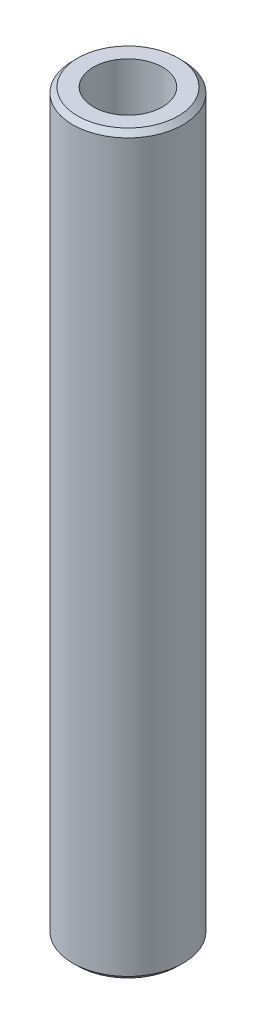
SolidWorks part; units mm, degrees
ref_plane "Front Plane" through (0, 0, 0) normal (0, 0, 1) x (1, 0, 0)
ref_plane "Top Plane" through (0, 0, 0) normal (0, 1, 0) x (1, 0, 0)
ref_plane "Right Plane" through (0, 0, 0) normal (1, 0, 0) x (0, 0, -1)
sketch "Sketch1" plane through (0, 0, 0) normal (0, 1, 0) x (1, 0, 0)
  circle A0 centre (0, 0) radius 45
  dimension "SHAFT_OD" = 90
extrude "Boss-Extrude1" add sketch "Sketch1" along normal blind 600
sketch "Sketch2" plane through (0, 0, 0) normal (0, 1, 0) x (1, 0, 0)
  circle A0 centre (0, 0) radius 28.1488
  dimension "BORE_D" = 56.2976
extrude "Cut-Extrude1" cut sketch "Sketch2" along normal through all
chamfer "Chamfer1" distance 4.1363 angle 44.395 2 edges at (0, 600, 45) (0, 0, 45) first distance on face at (0, 600, 45) first distance on face at (0, 0, 28.1488)
